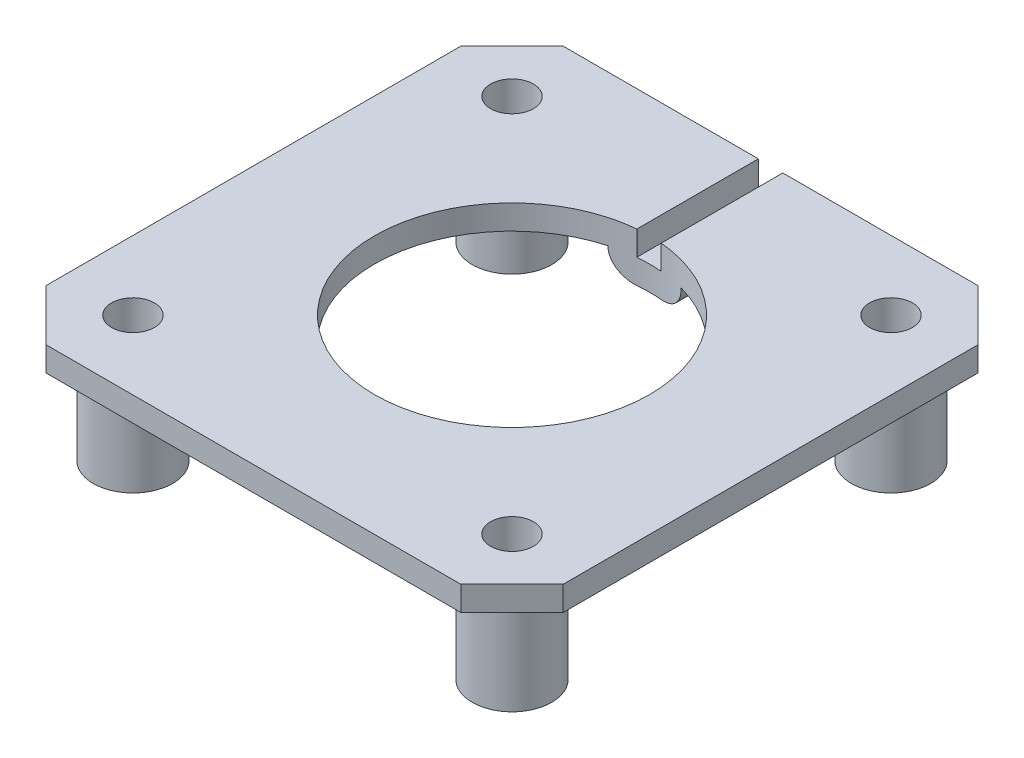
SolidWorks part; units mm, degrees
ref_plane "Front Plane" through (0, 0, 0) normal (0, 0, 1) x (1, 0, 0)
ref_plane "Top Plane" through (0, 0, 0) normal (0, 1, 0) x (1, 0, 0)
ref_plane "Right Plane" through (0, 0, 0) normal (1, 0, 0) x (0, 0, -1)
sketch "Sketch1" plane through (0, 0, 0) normal (0, 1, 0) x (1, 0, 0)
  circle A4 centre (-15.5, 15.5) radius 3.25
  dimension "D3" = 6.5
  dimension "D1" = 15.5
  dimension "D2" = 15.5
extrude "Boss-Extrude1" add sketch "Sketch1" along normal blind 10.3
mirror "Mirror2" about plane through (0, 0, 0) normal (1, 0, 0) of bodies 101
mirror "Mirror3" about plane through (0, 0, 0) normal (0, 0, 1) of bodies 101 102
sketch "Sketch2" plane through (0, 10.3, 0) normal (0, 1, 0) x (1, 0, 0)
  line L1 (-21.15, 21.15) -> (21.15, 21.15)
  line L2 (-21.15, 21.15) -> (-21.15, -21.15)
  line L3 (-21.15, -21.15) -> (21.15, -21.15)
  line L4 (21.15, 21.15) -> (21.15, -21.15)
  line L5 (-21.15, 21.15) -> (21.15, -21.15) construction
  line L6 (-21.15, -21.15) -> (21.15, 21.15) construction
  circle A0 centre (0, 0) radius 11.25
  dimension "D1" = 22.5
  dimension "D4" = 42.3
extrude "Boss-Extrude2" add sketch "Sketch2" against normal blind 2
sketch "Sketch3" plane through (0, 10.3, 0) normal (0, 1, 0) x (1, 0, 0)
  line L0 (-16.9631, 21.15) -> (-21.15, 16.9631)
  line L1 (21.15, 21.15) -> (-21.15, 21.15) construction
  line L2 (-21.15, 21.15) -> (-21.15, -21.15) construction
  line L3 (16.9631, -21.15) -> (21.15, -16.9631)
  line L4 (-21.15, -21.15) -> (21.15, -21.15) construction
  line L5 (21.15, -21.15) -> (21.15, 21.15) construction
  line L6 (-21.15, 16.9631) -> (-21.15, 21.15)
  line L7 (-21.15, 21.15) -> (-16.9631, 21.15)
  line L8 (21.15, -16.9631) -> (21.15, -21.15)
  line L9 (21.15, -21.15) -> (16.9631, -21.15)
  dimension "D1" = 45
  dimension "D2" = 53.9
extrude "Cut-Extrude1" cut sketch "Sketch3" against normal through all
mirror "Mirror4" about plane through (0, 0, 0) normal (0, 0, 1) of "Cut-Extrude1"
sketch "Sketch4" plane through (0, 0, 0) normal (0, -1, 0) x (1, 0, 0)
  circle A1 centre (15.5, -15.5) radius 3.25 construction
  circle A3 centre (15.5, -15.5) radius 1.75
  dimension "D1" = 3.5
extrude "Cut-Extrude2" cut sketch "Sketch4" against normal through all
mirror "Mirror5" about plane through (0, 0, 0) normal (1, 0, 0) of "Cut-Extrude2"
mirror "Mirror6" about plane through (0, 0, 0) normal (0, 0, 1) of "Mirror5"
sketch "Sketch6" plane through (0, 8.3, 0) normal (0, -1, 0) x (1, 0, 0)
  line L0 (0, -21.15) -> (0, -11.25) construction
  line L1 (16.9631, -21.15) -> (-16.9631, -21.15) construction
  line L2 (-3, -21.15) -> (-3, -10.8426)
  line L3 (3, -21.15) -> (3, -10.8426)
  line L4 (3, -21.15) -> (-3, -21.15)
  circle A0 centre (0, 0) radius 11.25 construction
  arc A3 (-3, -10.8426) -> (3, -10.8426) centre (0, 0) ccw
  point P7 (0, -18.325)
  dimension "D1" = 6
  dimension "D2" = 3
extrude "Boss-Extrude3" add sketch "Sketch6" along normal blind 2
sketch "Sketch7" plane through (0, 10.3, 0) normal (0, 1, 0) x (1, 0, 0)
  line L0 (0, 11.25) -> (0, 21.15) construction
  line L1 (16.9631, 21.15) -> (-16.9631, 21.15) construction
  line L2 (-1, 11.25) -> (-1, 21.15)
  line L3 (1, 11.25) -> (1, 21.15)
  circle A0 centre (0, 0) radius 11.25 construction
  arc A1 (-1, 11.25) -> (1, 11.25) centre (0, 11.25) ccw
  arc A2 (1, 21.15) -> (-1, 21.15) centre (0, 21.15) ccw
  point P6 (0, 16.2)
  dimension "D1" = 2
extrude "Cut-Extrude3" cut sketch "Sketch7" against normal blind 2
fillet "Fillet1" radius 2 2 edges at (3, 6.3, -15.9963) (-3, 6.3, -15.9963)
